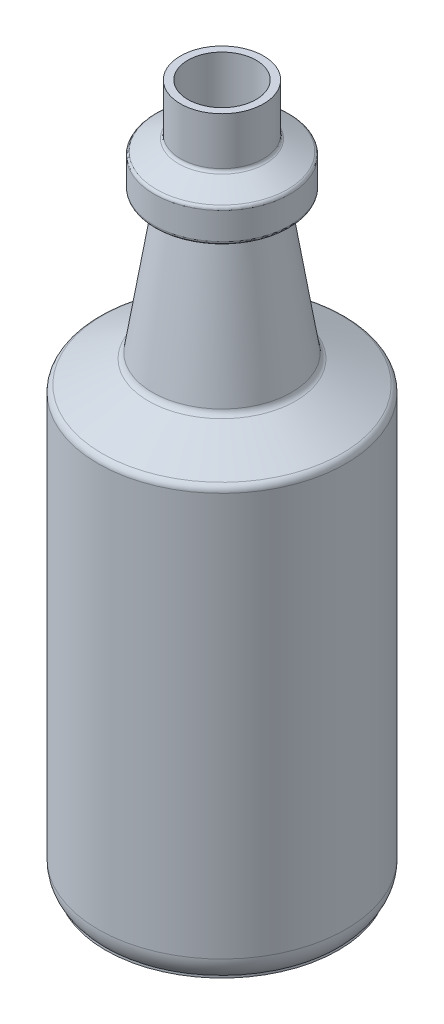
SolidWorks part; units mm, degrees
material "PET"
ref_plane "Front Plane" through (0, 0, 0) normal (0, 0, 1) x (1, 0, 0)
ref_plane "Top Plane" through (0, 0, 0) normal (0, 1, 0) x (1, 0, 0)
ref_plane "Right Plane" through (0, 0, 0) normal (1, 0, 0) x (0, 0, -1)
sketch "Sketch2" plane through (0, 0, 0) normal (0, 0, 1) x (1, 0, 0)
  line L0 (0, 0) -> (0, 241.3) construction
  line L1 (0, 0) -> (42.4942, 0)
  line L2 (42.4942, 0) -> (42.4942, 150.0124)
  line L3 (0, 241.3) -> (14.25, 241.3)
  line L4 (14.25, 241.3) -> (14.25, 224.2)
  line L5 (14.25, 224.2) -> (23.2416, 219.6658)
  line L6 (23.2416, 219.6658) -> (23.2416, 208.775)
  line L7 (23.2416, 208.775) -> (16.6162, 205.994)
  line L8 (16.6162, 205.994) -> (24.0587, 159.004)
  line L9 (24.0587, 159.004) -> (42.4942, 150.0124)
  dimension "D1" = 241.3
  dimension "D2" = 42.4942
  dimension "D3" = 150.0124
  dimension "D4" = 14.25
  dimension "D5" = 17.1
  dimension "D6" = 8.9916
  dimension "D8" = 2.781
  dimension "D9" = 46.99
  dimension "D10" = 8.9916
  dimension "D11" = 116
  dimension "D12" = 125
  dimension "D13" = 116.76
revolve "Revolve-Thin1" add sketch "Sketch2" angle 360 about L0 wall 2.54
cosmetic thread "Cosmetic Thread2" parameters "D2"=8.344
fillet "Fillet2" radius 1.27 2 edges at (0, 208.775, -23.2416) (0, 219.6658, -23.2416)
fillet "Fillet3" radius 2.54 1 edges at (0, 150.0124, -42.4942)
fillet "Fillet4" radius 10 1 edges at (0, 0, -42.4942)
fillet "Fillet5" radius 2.54 1 edges at (0, 159.004, -24.0587)
fillet "Fillet6" radius 0.635 1 edges at (0, 205.994, -16.6162)
fillet "Fillet7" radius 1.27 1 edges at (0, 224.2, -14.25)
sketch3d "3DSketch1"
  circle A1 centre (0, 238.76, 0) radius 11.71
  circle A2 centre (0, 238.76, 0) radius 11.71
  point P5 (0, 227.05, 0)
  point P7 (0, 227.05, 0)
  dimension "D1" = 0
extrude "Cut-Extrude1" cut sketch "3DSketch1" along direction (0, -1, 0) on the side against the normal blind 10 contours A2
